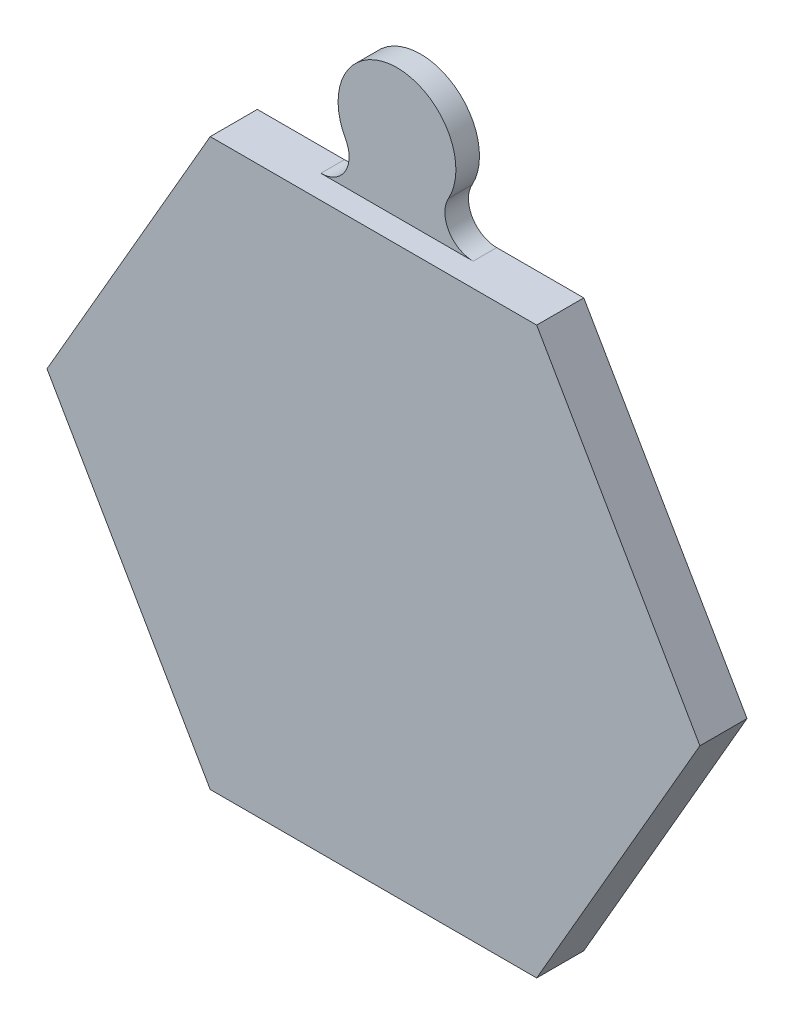
SolidWorks part; units mm, degrees
ref_plane "前视基准面" through (0, 0, 0) normal (0, 0, 1) x (1, 0, 0)
ref_plane "上视基准面" through (0, 0, 0) normal (0, 1, 0) x (1, 0, 0)
ref_plane "右视基准面" through (0, 0, 0) normal (1, 0, 0) x (0, 0, -1)
sketch "草图1" plane through (0, 0, 0) normal (0, 0, 1) x (1, 0, 0)
  line L1 (69.282, 0) -> (34.641, 60)
  line L2 (34.641, 60) -> (-34.641, 60)
  line L3 (-34.641, 60) -> (-69.282, 0)
  line L4 (-69.282, 0) -> (-34.641, -60)
  line L5 (-34.641, -60) -> (34.641, -60)
  line L6 (34.641, -60) -> (69.282, 0)
  circle A0 centre (0, 0) radius 60 construction
  point P1 (0, 0)
  dimension "D1" = 120
extrude "凸台-拉伸1" add sketch "草图1" along normal blind 10
sketch "草图2" plane through (0, 0, 0) normal (0, 0, -1) x (-1, 0, 0)
  line L2 (-34.641, 60) -> (34.641, 60) construction
  line L3 (-16.1632, 60) -> (16.1632, 60)
  line L4 (0, 19.7238) -> (0, 10.5872) construction
  arc A0 (10.9211, 68.9189) -> (-10.9211, 68.9189) centre (0, 75) ccw
  arc A1 (10.9211, 68.9189) -> (16.1632, 60) centre (16.1632, 66) ccw
  arc A2 (-10.9211, 68.9189) -> (-16.1632, 60) centre (-16.1632, 66) cw
  point P1 (0, 72.7106)
  point P9 (0, 16.1627)
  dimension "D1" = 25
  dimension "D2" = 12
  dimension "D3" = 15
extrude "凸台-拉伸2" add sketch "草图2" against normal blind 5
sketch "草图3" plane through (0, 0, 0) normal (0, 0, -1) x (-1, 0, 0)
  line L0 (-16.1632, -60) -> (16.1632, -60) construction
  line L1 (34.641, -60) -> (-34.641, -60) construction
  line L2 (-16.2776, -60) -> (0, -60)
  line L3 (0, 1.3937) -> (0, -16.0678) construction
  line L4 (16.2776, -60) -> (-16.2776, -60)
  arc A6 (10.9211, -51.0811) -> (-10.9211, -51.0811) centre (0, -45) ccw construction
  arc A7 (10.9211, -51.0811) -> (16.1632, -60) centre (16.1632, -54) ccw construction
  arc A8 (-10.9211, -51.0811) -> (-16.1632, -60) centre (-16.1632, -54) cw construction
  arc A9 (11.0085, -51.1297) -> (-11.0268, -51.0968) centre (0, -45) ccw
  arc A10 (-16.2776, -60) -> (-11.0268, -51.0968) centre (-16.2776, -54) ccw
  arc A11 (11.0085, -51.1297) -> (-11.0085, -51.1297) centre (0, -45) ccw construction
  arc A12 (16.2776, -60) -> (11.0268, -51.0968) centre (16.2776, -54) cw
  dimension "D1" = 6
  dimension "D2" = 12.5
  dimension "D5" = 6
  dimension "D3" = 15
  dimension "D4" = 0.1
extrude "切除-拉伸2" cut sketch "草图3" against normal blind 5 contours A10 A12 A9 region at (0, -47.1072, 0)
ref_axis "基准轴1" through (0, 0, 0) along (0, 0, -1)
